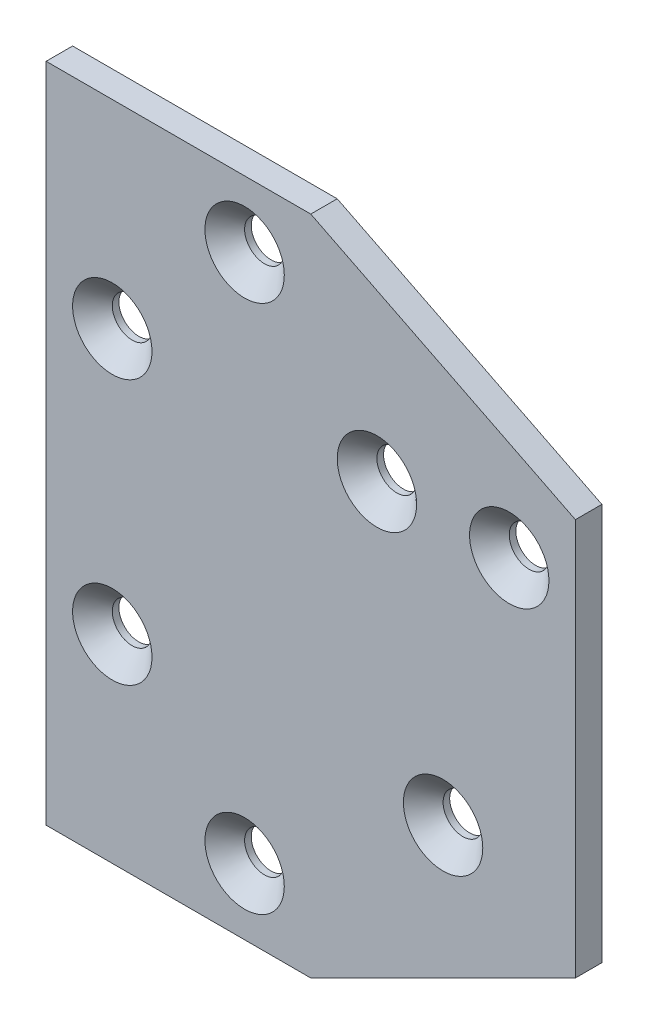
SolidWorks part; units mm, degrees
material "Aluminum 6105-T5"
ref_plane "Front Plane" through (0, 0, 0) normal (0, 0, 1) x (1, 0, 0)
ref_plane "Top Plane" through (0, 0, 0) normal (0, 1, 0) x (1, 0, 0)
ref_plane "Right Plane" through (0, 0, 0) normal (1, 0, 0) x (0, 0, -1)
sketch "Sketch1" plane through (0, 0, 0) normal (0, 0, 1) x (1, 0, 0)
  line L0 (20, 50) -> (60, 30)
  line L1 (-20, -50) -> (20, -50)
  line L2 (-20, -50) -> (-20, 50)
  line L3 (-20, 50) -> (20, 50)
  line L4 (20, -50) -> (20, 50)
  line L5 (-20, -50) -> (20, 50) construction
  line L6 (-20, 50) -> (20, -50) construction
  line L7 (60, -30) -> (20, -30)
  line L8 (60, -30) -> (60, 30)
  line L9 (60, 30) -> (20, 30)
  line L10 (20, -30) -> (20, 30)
  line L11 (60, -30) -> (20, 30) construction
  line L12 (60, 30) -> (20, -30) construction
  line L13 (20, -50) -> (60, -30)
  line L14 (0, 0) -> (40, 0) construction
  point P0 (0, 0)
  point P9 (40, 0)
  dimension "D1" = 60
  dimension "D2" = 40
  dimension "D3" = 40
  dimension "D4" = 100
extrude "Boss-Extrude1" add sketch "Sketch1" along normal mid plane 4 contours L1 L4 L3 L2 | L9 L0 L4 | L8 L9 L4 L7 | L4 L13 L7 region at (0, 0, 0) region at (33.3333, 36.6667, 0) region at (40, 0, 0) region at (33.3333, -36.6667, 0)
sketch "Sketch2" plane through (0, 0, 2) normal (0, 0, 1) x (1, 0, 0)
  line L0 (-10, 20) -> (-10, -20) construction
  line L1 (-10, -20) -> (40, -20) construction
  line L2 (10, -40) -> (10, 40) construction
  line L3 (30, 20) -> (50, 20) construction
  line L4 (-10, 20) -> (30, 20) construction
  circle A0 centre (-10, 20) radius 3
  circle A2 centre (-10, -20) radius 3
  circle A3 centre (10, -40) radius 3
  circle A4 centre (40, -20) radius 3
  circle A5 centre (30, 20) radius 3
  circle A6 centre (50, 20) radius 3
  circle A7 centre (10, 40) radius 3
  dimension "D8" = 6
  dimension "D1" = 20
  dimension "D2" = 10
  dimension "D3" = 20
  dimension "D4" = 20
  dimension "D5" = 20
  dimension "D6" = 40
  dimension "D7" = 20
  dimension "D9" = 10
extrude "Cut-Extrude1" cut sketch "Sketch2" against normal through all
chamfer "Chamfer1" distance 3 angle 45 7 edges at (13, -40, 2) (43, -20, 2) (-7, -20, 2) (53, 20, 2) (33, 20, 2) (13, 40, 2) (-7, 20, 2)
fillet "Fillet1" [suppressed] radius 1
